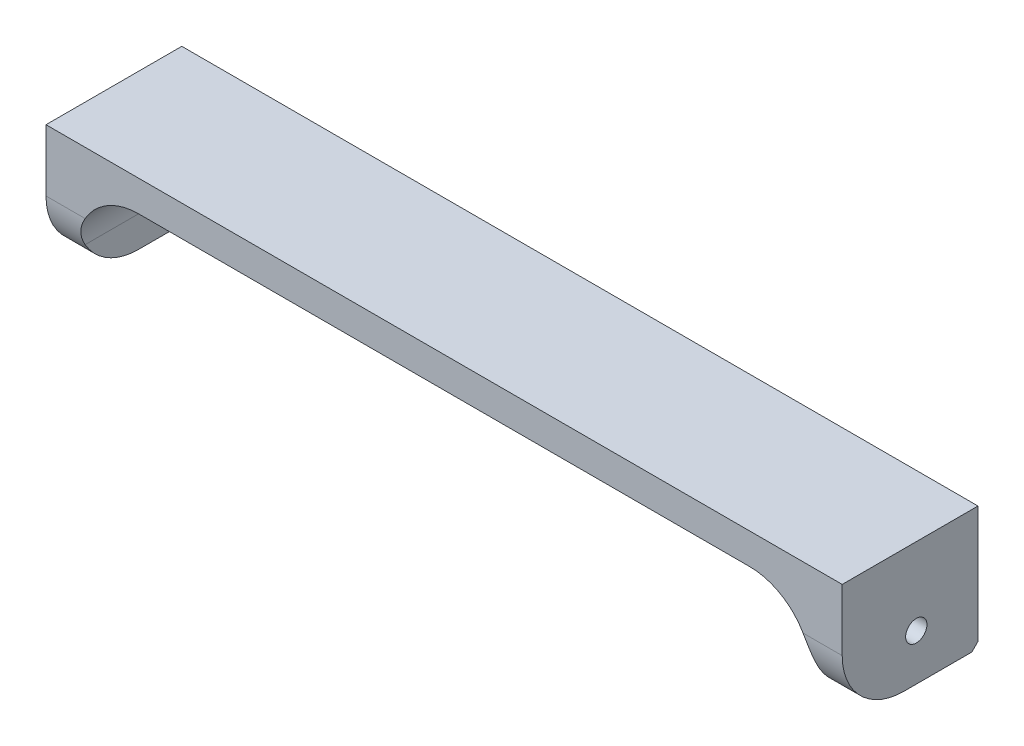
SolidWorks part; units mm, degrees
material "ABS"
ref_plane "Top Plane" through (0, 0, 0) normal (0, 0, 1) x (1, 0, 0)
ref_plane "Front Plane" through (0, 0, 0) normal (0, 1, 0) x (1, 0, 0)
ref_plane "Right Plane" through (0, 0, 0) normal (1, 0, 0) x (0, 0, -1)
sketch "Sketch1" plane through (0, 0, 0) normal (0, 0, 1) x (1, 0, 0)
  line L0 (-64.5, 10) -> (64.5, 10)
  line L1 (64.5, 10) -> (64.5, -10)
  line L2 (64.5, -10) -> (59.5, -10)
  line L3 (59.5, -10) -> (59.5, 5)
  line L4 (59.5, 5) -> (-59.5, 5)
  line L5 (-59.5, 5) -> (-59.5, -10)
  line L6 (-59.5, -10) -> (-64.5, -10)
  line L7 (-64.5, -10) -> (-64.5, 10)
  point P3 (0, 10)
  dimension "D1" = 129
  dimension "D2" = 5
  dimension "D3" = 5
  dimension "D4" = 5
  dimension "D5" = 15
  dimension "D6" = 15
  dimension "D7" = 10
extrude "Boss-Extrude1" add sketch "Sketch1" along normal blind 22
fillet "Fillet1" radius 10 2 edges at (59.5, 5, 11) (-59.5, 5, 11)
sketch "Sketch2" plane through (64.5, 0, 0) normal (1, 0, 0) x (0, 0, -1)
  line L0 (-22, -10) -> (0, -10) construction
  line L1 (0, -10) -> (0, 10) construction
  circle A0 centre (-10, -2.5) radius 1.725
  dimension "D3" = 3.45
  dimension "D1" = 7.5
  dimension "D2" = 10
extrude "Cut-Extrude1" cut sketch "Sketch2" against normal through all
sketch "Sketch3" plane through (59.5, 0, 0) normal (-1, 0, 0) x (0, 0, 1)
  circle A0 centre (10, -2.5) radius 2.8
  dimension "D1" = 5.6
extrude "Cut-Extrude2" cut sketch "Sketch3" along normal blind 119
fillet "Fillet2" radius 10 2 edges at (62, -10, 22) (-62, -10, 22)
chamfer "Chamfer1" distance 1 angle 45 2 edges at (62, -10, 0) (-62, -10, 0)
